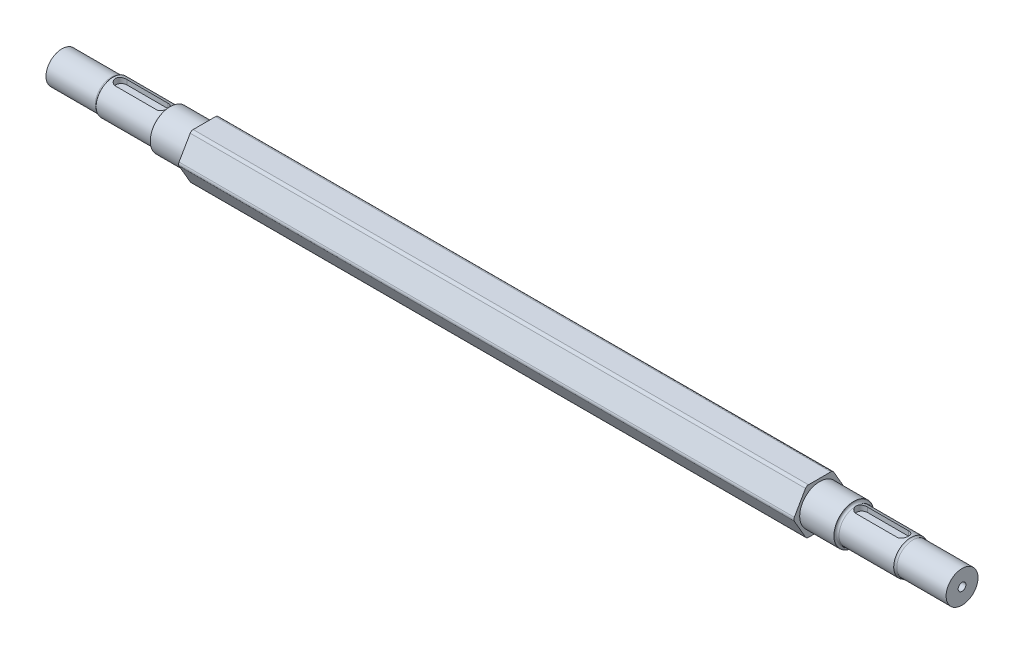
SolidWorks part; units mm, degrees
material "A286 Iron Base Superalloy"
ref_plane "Front Plane" through (0, 0, 0) normal (0, 0, 1) x (1, 0, 0)
ref_plane "Top Plane" through (0, 0, 0) normal (0, 1, 0) x (1, 0, 0)
ref_plane "Right Plane" through (0, 0, 0) normal (1, 0, 0) x (0, 0, -1)
sketch "Sketch1" plane through (0, 0, 0) normal (1, 0, 0) x (0, 0, -1)
  line L1 (23.094, 0) -> (11.547, 20)
  line L2 (11.547, 20) -> (-11.547, 20)
  line L3 (-11.547, 20) -> (-23.094, 0)
  line L4 (-23.094, 0) -> (-11.547, -20)
  line L5 (-11.547, -20) -> (11.547, -20)
  line L6 (11.547, -20) -> (23.094, 0)
  circle A0 centre (0, 0) radius 20 construction
  point P1 (0, 20)
  dimension "D1" = 40
extrude "Boss-Extrude1" add sketch "Sketch1" along normal mid plane 540
sketch "Sketch2" plane through (0, 0, 0) normal (0, 0, 1) x (1, 0, 0)
  line L0 (270, 17.5) -> (300, 17.5)
  line L1 (270, 20) -> (270, 0) construction
  line L2 (300, 17.5) -> (300, 15)
  line L3 (300, 15) -> (350, 15)
  line L4 (350, 15) -> (350, 14)
  line L5 (350, 14) -> (395, 14)
  line L6 (395, 14) -> (395, 0)
  line L7 (395, 0) -> (270, 0)
  line L8 (270, 0) -> (-270, 0) construction
  line L9 (270, 0) -> (270, 17.5)
  dimension "D1" = 30
  dimension "D2" = 50
  dimension "D3" = 45
  dimension "D4" = 17.5
  dimension "D5" = 15
  dimension "D6" = 14
revolve "Revolve1" add sketch "Sketch2" angle 360 about L7
fillet "Fillet1" radius 2 2 edges at (350, 14, 0) (300, 15, 0)
ref_plane "Plane1" through (0, 15, 0) normal (0, 1, 0) x (1, 0, 0)
sketch "Sketch3" plane through (0, 15, 0) normal (0, 1, 0) x (1, 0, 0)
  line L0 (307, 0) -> (343, 0) construction
  line L1 (307, 5) -> (343, 5)
  line L2 (307, -5) -> (343, -5)
  line L3 (350, -15) -> (350, 15) construction
  line L5 (300, -17) -> (300, 17) construction
  arc A0 (307, 5) -> (307, -5) centre (307, 0) ccw
  arc A1 (343, -5) -> (343, 5) centre (343, 0) ccw
  point P3 (325, 0)
  point P10 (348, 0)
  point P11 (302, 0)
  dimension "D1" = 2
  dimension "D2" = 10
  dimension "D3" = 2
extrude "Cut-Extrude1" cut sketch "Sketch3" against normal blind 5
mirror "Mirror1" about plane through (0, 0, 0) normal (1, 0, 0) of "Cut-Extrude1", "Fillet1", "Revolve1"
fillet "Fillet2" radius 3 6 edges at (0, -20, -11.547) (0, -20, 11.547) (0, 0, 23.094) (0, 20, 11.547) (0, 0, -23.094) (0, 20, -11.547)
hole_wizard "Tap Drill for M8 Tap1" positions "Sketch4" profile "Sketch5" hole size "M8" standard "ISO"
sketch "Sketch4" plane through (395, 0, 0) normal (1, 0, 0) x (0, 0, -1)
  point P0 (0, 0)
sketch "Sketch5" plane through (395, 0, 0) normal (0, 1, 0) x (0, 0, -1)
  line L0 (0, 0) -> (0, 27.5)
  line L1 (0, 27.5) -> (3.4, 25.4571)
  line L2 (3.4, 25.4571) -> (3.4, 0.025)
  line L3 (3.4, 0.025) -> (3.425, 0)
  line L5 (3.425, 0) -> (0, 0)
  line L6 (-3.4, 0.025) -> (-3.425, 0) construction
  line L10 (0, 27.5) -> (-3.4, 25.4571) construction
  line L11 (0, -6.35) -> (0, 107.95) construction
  dimension "Hole Dia." = 6.8
  dimension "Hole Depth" = 27.5
  dimension "Near C'Sink Dia." = 6.85
  dimension "Near C'Sink Angle" = 90
  dimension "Drill Angle" = 118
mirror "Mirror2" about plane through (0, 0, 0) normal (1, 0, 0) of "Tap Drill for M8 Tap1"
